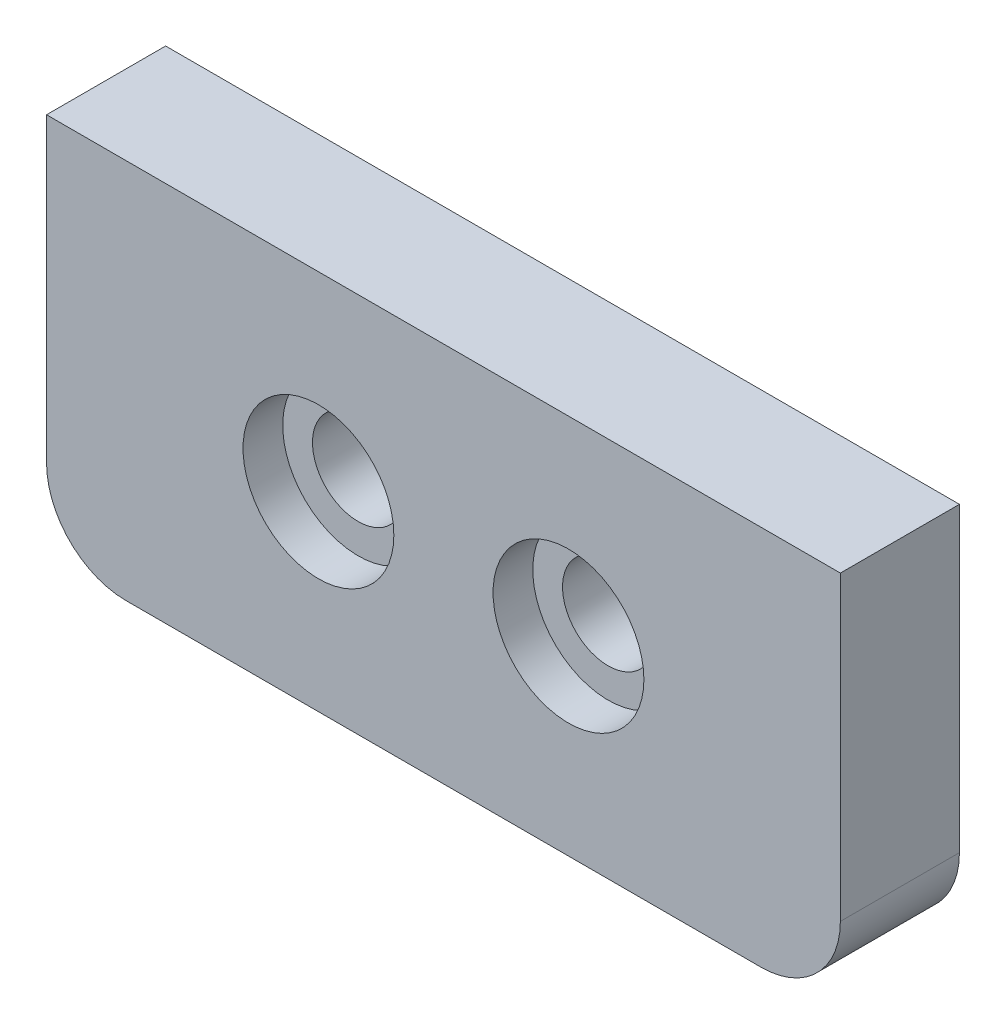
SolidWorks part; units mm, degrees
ref_plane "Front Plane" through (0, 0, 0) normal (0, 0, 1) x (1, 0, 0)
ref_plane "Top Plane" through (0, 0, 0) normal (0, 1, 0) x (1, 0, 0)
ref_plane "Right Plane" through (0, 0, 0) normal (1, 0, 0) x (0, 0, -1)
sketch "Sketch1" plane through (0, 0, 0) normal (0, 0, 1) x (1, 0, 0)
  line L0 (0, 4.8) -> (20, 4.8) construction
  line L1 (0, 0) -> (20, 0)
  line L2 (0, 0) -> (0, 9.6)
  line L3 (0, 9.6) -> (20, 9.6)
  line L4 (20, 0) -> (20, 9.6)
  line L5 (10, 9.6) -> (10, 0) construction
  circle A0 centre (6.85, 4.8) radius 1.15
  circle A1 centre (13.15, 4.8) radius 1.15
  point P15 (7.8339, 5.3953)
  dimension "D3" = 2.3
  dimension "D1" = 20
  dimension "D2" = 9.6
  dimension "D4" = 3.15
  dimension "D5" = 6.3
extrude "Boss-Extrude1" add sketch "Sketch1" along normal blind 3
fillet "Fillet1" radius 2 2 edges at (0, 0, 1.5) (20, 0, 1.5)
sketch "Sketch2" plane through (0, 0, 3) normal (0, 0, 1) x (1, 0, 0)
  circle A0 centre (6.85, 4.8) radius 1.9
  circle A1 centre (13.15, 4.8) radius 1.9
  dimension "D1" = 3.8
extrude "Cut-Extrude1" cut sketch "Sketch2" against normal blind 1
